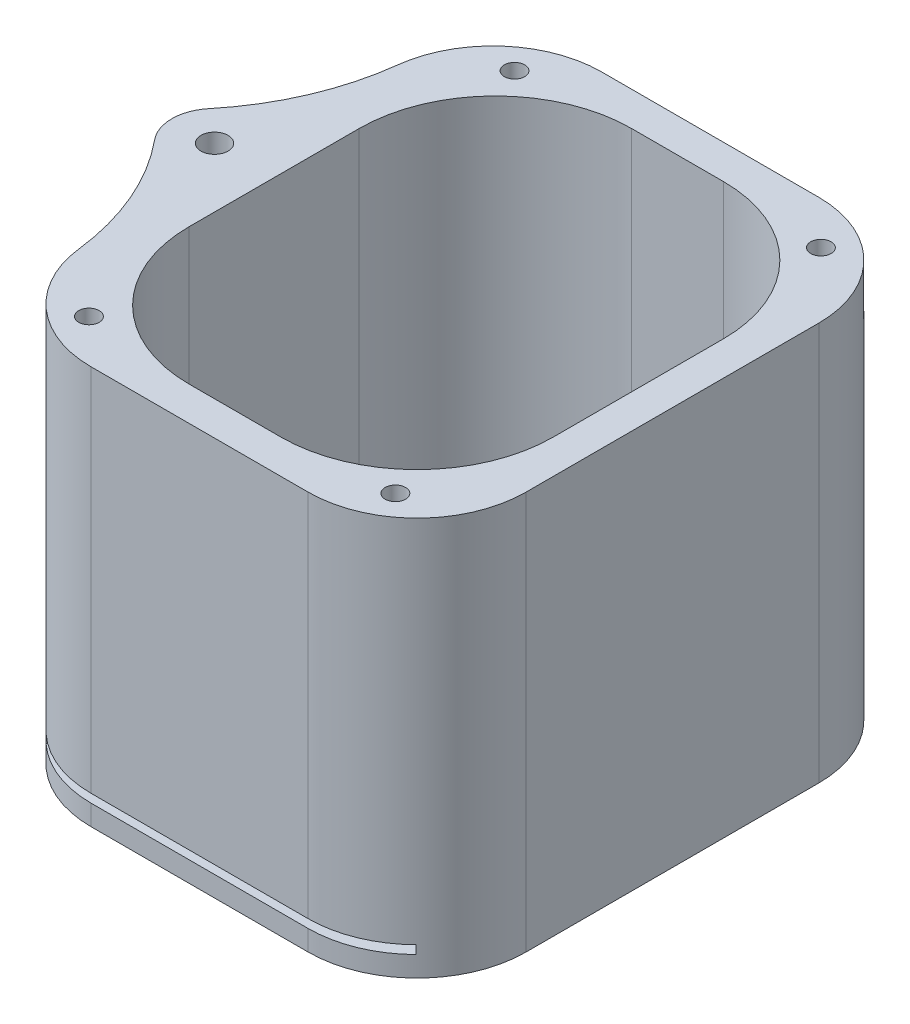
SolidWorks part; units mm, degrees
ref_plane "Front Plane" through (0, 0, 0) normal (0, 0, 1) x (1, 0, 0)
ref_plane "Top Plane" through (0, 0, 0) normal (0, 1, 0) x (1, 0, 0)
ref_plane "Right Plane" through (0, 0, 0) normal (1, 0, 0) x (0, 0, -1)
sketch "Sketch1" plane through (0, 0, 0) normal (0, 0, 1) x (1, 0, 0)
  line L0 (0, 0) -> (0, 127) construction
  line L1 (4, 0) -> (4, 127)
  line L2 (4, 127) -> (12.5, 127)
  line L3 (12.5, 127) -> (12.5, 10)
  line L4 (12.5, 10) -> (7.5, 10)
  line L5 (7.5, 10) -> (7.5, 0)
  line L6 (7.5, 0) -> (4, 0)
  dimension "D1" = 127
  dimension "D2" = 8
  dimension "D3" = 15
  dimension "D4" = 25
  dimension "D5" = 10
revolve "Revolve1" add sketch "Sketch1" angle 360 about L0
sketch "Sketch3" plane through (0, 0, 0) normal (0, -1, 0) x (1, 0, 0)
  line L0 (0, 0) -> (7.5, 0) construction
  line L1 (7.5, 13.0069) -> (21.0981, 13.0069)
  line L2 (7.5, 13.0069) -> (7.5, -13.0069)
  line L3 (7.5, -13.0069) -> (21.0981, -13.0069)
  line L4 (21.0981, 13.0069) -> (21.0981, -13.0069)
  circle A0 centre (0, 0) radius 7.5 construction
  dimension "D1" = 26.0139
extrude "Cut-Extrude1" cut sketch "Sketch3" against normal up to next
sketch "Sketch2" plane through (0, 0, 0) normal (0, 0, 1) x (1, 0, 0)
  line L1 (7.5, 127) -> (134.5, 127)
  line L2 (7.5, 127) -> (7.5, 10)
  line L3 (7.5, 10) -> (134.5, 10)
  line L4 (134.5, 127) -> (134.5, 10)
  line L6 (-12.5, 10) -> (7.5, 10) construction
  line L7 (7.5, 127) -> (-12.5, 127) construction
  line L8 (7.5, 0) -> (7.5, 10) construction
  dimension "D1" = 127
extrude "Boss-Extrude1" add sketch "Sketch2" along normal blind 75 and the other way blind 75 separate body
sketch "Sketch4" plane through (0, 127, 0) normal (0, 1, 0) x (1, 0, 0)
  line L0 (7.5, 75) -> (7.5, -75) construction
  line L1 (7.5, 55.6776) -> (7.5, 10)
  line L2 (0, 0) -> (-34.0978, 0) construction
  line L3 (7.5, -55.6776) -> (7.5, -10)
  arc A0 (-9.6429, 7.9539) -> (7.5, 55.6776) centre (-67.5, 55.6776) ccw
  arc A1 (7.5, 10) -> (7.5, -10) centre (0, 0) ccw construction
  arc A2 (7.5, 10) -> (-9.6429, 7.9539) centre (0, 0) ccw
  arc A3 (7.5, -10) -> (-9.6429, -7.9539) centre (0, 0) cw
  arc A4 (-9.6429, -7.9539) -> (7.5, -55.6776) centre (-67.5, -55.6776) cw
  line M5 (7.5, 75) -> (7.5, -75)
  dimension "D1" = 75
extrude "Boss-Extrude3" add sketch "Sketch4" against normal up to surface (117 mm away) contours A3 A4 M5 | A2 A0 M5 region at (3.2984, 127, 22.4464) region at (3.2984, 127, -22.4464) up to face at (0.625, 10, -1.875)
sketch "Sketch5" plane through (0, 127, 0) normal (0, 1, 0) x (1, 0, 0)
  line L0 (134.5, -75) -> (7.5, -75) construction
  line L1 (134.5, 75) -> (134.5, -75) construction
  line L2 (134.5, 75) -> (7.5, 75) construction
  line L3 (134.5, -75) -> (7.5, -75)
  line L4 (134.5, 75) -> (134.5, -75)
  line L5 (134.5, 75) -> (7.5, 75)
  line L6 (124.5, 65) -> (17.5, 65)
  line L7 (124.5, 65) -> (124.5, -65)
  line L8 (124.5, -65) -> (17.5, -65)
  line L9 (17.5, 65) -> (17.5, -65)
  line L10 (124.5, 65) -> (7.5, 65) construction
  line L11 (124.5, -65) -> (7.5, -65) construction
  dimension "D2" = 10
  dimension "D1" = 10
extrude "Cut-Extrude2" cut sketch "Sketch5" against normal through all both and the other way through all contours L6 L9 L8 L7 region at (71, 127, 0)
sketch "Sketch6" plane through (0, 0, 75) normal (0, 0, 1) x (1, 0, 0)
  line L0 (134.5, 10) -> (134.5, 127) construction
  line L1 (125, 18.5) -> (17, 18.5)
  line L2 (125, 18.5) -> (125, 16)
  line L3 (125, 16) -> (17, 16)
  line L4 (17, 18.5) -> (17, 16)
  line L5 (7.5, 10) -> (7.5, 127) construction
  line L6 (7.5, 10) -> (134.5, 10) construction
  dimension "D1" = 9.5
  dimension "D2" = 9.5
  dimension "D3" = 2.5
  dimension "D4" = 6
extrude "Cut-Extrude3" cut sketch "Sketch6" against normal through all and the other way through all
fillet "Fillet3" radius 40 8 edges at (17.5, 72.75, 65) (17.5, 72.75, -65) (124.5, 72.75, 65) (124.5, 72.75, -65) (17.5, 13, 65) (17.5, 13, -65) (124.5, 13, -65) (124.5, 13, 65)
fillet "Fillet2" radius 32 4 edges at (7.5, 68.5, -75) (134.5, 68.5, -75) (7.5, 68.5, 75) (134.5, 68.5, 75)
chamfer "Chamfer1" distance 1 angle 45 1 edges at (0, 0, -7.5)
sketch "Sketch7" plane through (0, 127, 0) normal (0, 1, 0) x (1, 0, 0)
  line L0 (0, 0) -> (25.6232, 0) construction
  line L1 (115.6232, -62.5) -> (25.6232, -62.5) construction
  line L2 (115.6232, -62.5) -> (115.6232, 62.5) construction
  line L3 (115.6232, 62.5) -> (25.6232, 62.5) construction
  line L4 (25.6232, -62.5) -> (25.6232, 62.5) construction
  line L5 (70.6232, -75) -> (70.6232, -62.5)
  line L6 (102.5, -75) -> (38.7463, -75) construction
  circle A0 centre (115.6232, -62.5) radius 3
  circle A1 centre (25.6232, -62.5) radius 3
  circle A2 centre (115.6232, 62.5) radius 3
  circle A3 centre (25.6232, 62.5) radius 3
  point P5 (0, 0)
  point P6 (0, 0)
  point P16 (0, 0)
  point P17 (0, 0)
  point P19 (114.705, 62.5)
  point P21 (24.5749, 62.5)
  dimension "D3" = 6
  dimension "D1" = 125
  dimension "D2" = 90
extrude "Cut-Extrude4" cut sketch "Sketch7" against normal blind 8 contours A0 | A1 | A3 | A2 region at (115.6232, 127, 62.5) region at (25.6232, 127, 62.5) region at (115.6232, 127, -62.5) region at (25.6232, 127, -62.5)
